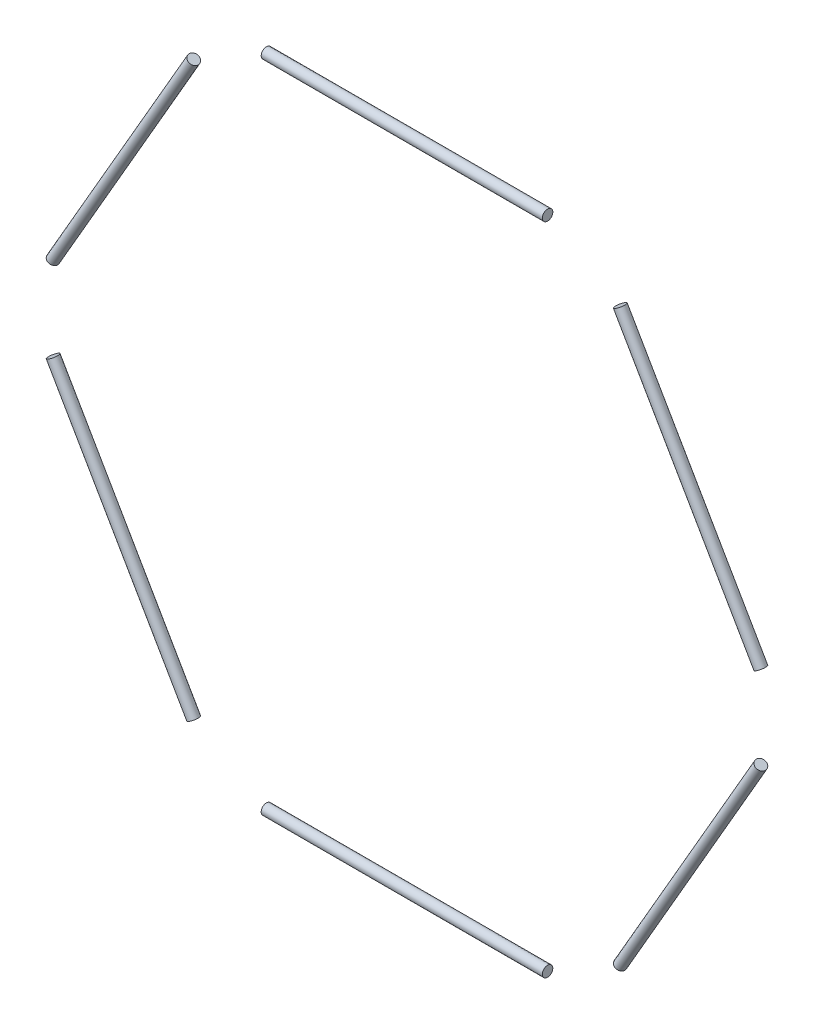
SolidWorks part; units mm, degrees
material "Plain Carbon Steel"
ref_plane "Front Plane" through (0, 0, 0) normal (0, 0, 1) x (1, 0, 0)
ref_plane "Top Plane" through (0, 0, 0) normal (0, 1, 0) x (1, 0, 0)
ref_plane "Right Plane" through (0, 0, 0) normal (1, 0, 0) x (0, 0, -1)
sketch "Master Sketch" plane through (0, 0, 0) normal (0, 0, 1) x (1, 0, 0)
  line L0 (0, 69) -> (0, -69) construction
  line L1 (68.4737, 0) -> (34.2369, 59.3)
  line L2 (34.2369, 59.3) -> (-34.2369, 59.3)
  line L3 (-34.2369, 59.3) -> (-68.4737, 0)
  line L4 (-68.4737, 0) -> (-34.2369, -59.3)
  line L5 (-34.2369, -59.3) -> (34.2369, -59.3)
  line L6 (34.2369, -59.3) -> (68.4737, 0)
  line L7 (20.1736, 65.985) -> (20.1736, -65.985)
  line L8 (-20.1736, 65.985) -> (-20.1736, -65.985)
  line L9 (-20.1736, -65.985) -> (20.1736, 65.985) construction
  line L10 (-18.1736, 64.4881) -> (-18.1736, -64.4881)
  line L11 (18.1736, 64.4881) -> (18.1736, -64.4881)
  line L12 (-24.1736, 59.3) -> (-24.1736, -59.3)
  line L13 (24.1736, 59.3) -> (24.1736, -59.3)
  line L14 (-24.1736, 56.3) -> (24.1736, 56.3)
  line L15 (-24.1736, -56.3) -> (24.1736, -56.3)
  line L16 (-68.4737, 0) -> (68.4737, 0) construction
  line L17 (-24.1736, 57.2) -> (24.1736, 57.2)
  line L18 (-24.1736, 55.4) -> (24.1736, 55.4)
  line L19 (-24.1736, -55.4) -> (24.1736, -55.4)
  line L20 (-24.1736, -57.2) -> (24.1736, -57.2)
  line L21 (-24.1736, 57.3) -> (24.1736, 57.3)
  line L22 (-24.1736, 55.3) -> (24.1736, 55.3)
  line L23 (-24.1736, -55.3) -> (24.1736, -55.3)
  line L24 (-24.1736, -57.3) -> (24.1736, -57.3)
  circle A0 centre (0, 0) radius 67
  circle A1 centre (0, 0) radius 59.3 construction
  circle A2 centre (0, 0) radius 69
  circle A3 centre (0, 0) radius 65
  point P2 (0, 0)
  point P12 (0, 0)
  point P18 (0, 0)
  point P21 (0, -67)
  point P22 (0, 67)
  point P24 (0, 67)
  point P25 (0, 67)
  point P29 (0, 67)
  point P48 (0, 0)
  point P55 (0, 0)
  point P66 (0, 0)
  point P74 (0, 0)
revolve "Revolve1" add sketch "Master Sketch" angle 360 about L14 region at (22.1736, 56.75, 0) region at (19.1736, 56.75, 0) region at (0, 56.75, 0) region at (-19.1736, 56.75, 0) region at (-22.1736, 56.75, 0)
ref_axis "Axis1" through (0, 0, 0) along (0, 0, 1)
pattern_circular "CirPattern1" count 6 over 360 about axis through (0, 0, 0) along (0, 0, 1) of bodies 101
